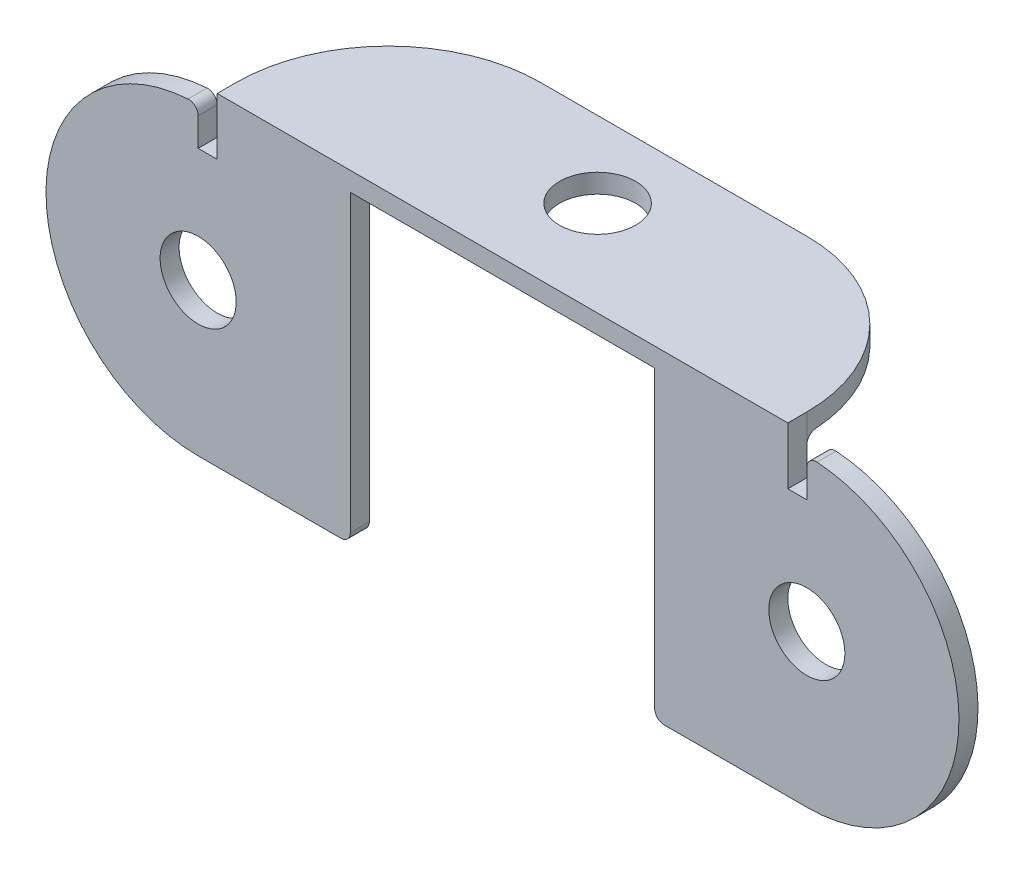
SolidWorks part; units mm, degrees
ref_plane "Front Plane" through (0, 0, 0) normal (0, 0, 1) x (1, 0, 0)
ref_plane "Top Plane" through (0, 0, 0) normal (0, 1, 0) x (1, 0, 0)
ref_plane "Right Plane" through (0, 0, 0) normal (1, 0, 0) x (0, 0, -1)
sketch "Sketch1" plane through (0, 0, 0) normal (0, 0, 1) x (1, 0, 0)
  line L1 (-12.7, -12.7) -> (12.7, -12.7)
  line L2 (-12.7, -12.7) -> (-12.7, 12.7)
  line L3 (-12.7, 12.7) -> (12.7, 12.7)
  line L4 (12.7, -12.7) -> (12.7, 12.7)
  line L5 (-12.7, -12.7) -> (12.7, 12.7) construction
  line L6 (-12.7, 12.7) -> (12.7, -12.7) construction
  line L9 (12.7, -12.7) -> (25.4, -12.7)
  line L10 (-25.4, -12.7) -> (-12.7, -12.7)
  line L21 (-25.4, 12.7) -> (-25.4, 14.2875)
  line L22 (-25.4, 14.2875) -> (25.4, 14.2875)
  line L23 (25.4, 14.2875) -> (25.4, 12.7)
  circle A0 centre (-25.4, 0) radius 12.7
  circle A1 centre (-25.4, 0) radius 11.43 construction
  circle A2 centre (-25.4, 0) radius 3.175
  circle A3 centre (25.4, 0) radius 12.7
  circle A4 centre (25.4, 0) radius 3.175
  point P0 (0, 0)
  dimension "D3" = 25.4
  dimension "D4" = 1.27
  dimension "D5" = 6.35
  dimension "D1" = 25.4
  dimension "D2" = 1.5875
extrude "Boss-Extrude1" add sketch "Sketch1" along normal blind 1.5875
sketch "Sketch3" plane through (0, 14.2875, 0) normal (0, 1, 0) x (1, 0, 0)
  line L0 (0, 0) -> (0, 12.7) construction
  line L1 (-25.4, 12.7) -> (25.4, 12.7)
  line L2 (-25.4, 12.7) -> (-25.4, 0)
  line L3 (-25.4, 0) -> (25.4, 0)
  line L4 (25.4, 12.7) -> (25.4, 0)
  circle A0 centre (0, 6.35) radius 3.175
  dimension "D2" = 6.35
  dimension "D1" = 12.7
extrude "Boss-Extrude2" add sketch "Sketch3" against normal blind 1.5875
sketch "Sketch5" plane through (0, 0, 1.5875) normal (0, 0, 1) x (1, 0, 0)
  line L1 (-25.4, 14.2875) -> (-23.8125, 14.2875)
  line L2 (-25.4, 14.2875) -> (-25.4, 9.525)
  line L3 (-25.4, 9.525) -> (-23.8125, 9.525)
  line L4 (-23.8125, 14.2875) -> (-23.8125, 9.525)
  line L5 (25.4, 14.2875) -> (23.8125, 14.2875)
  line L6 (25.4, 14.2875) -> (25.4, 9.525)
  line L7 (25.4, 9.525) -> (23.8125, 9.525)
  line L8 (23.8125, 14.2875) -> (23.8125, 9.525)
  point P10 (0, 0)
  dimension "D1" = 1.5875
  dimension "D2" = 4.7625
extrude "Cut-Extrude1" cut sketch "Sketch5" against normal through all both and the other way through all
fillet "Fillet2" radius 0.7937 5 edges at (-18.2562, 12.7, 0) (25.4, 12.7, 0.7937) (-25.4, 12.7, 0.7937) (12.7, -12.7, 0.7937) (-12.7, -12.7, 0.7937)
fillet "Fillet3" radius 12.7 2 edges at (23.8125, 13.4938, -12.7) (-23.8125, 13.4938, -12.7)
